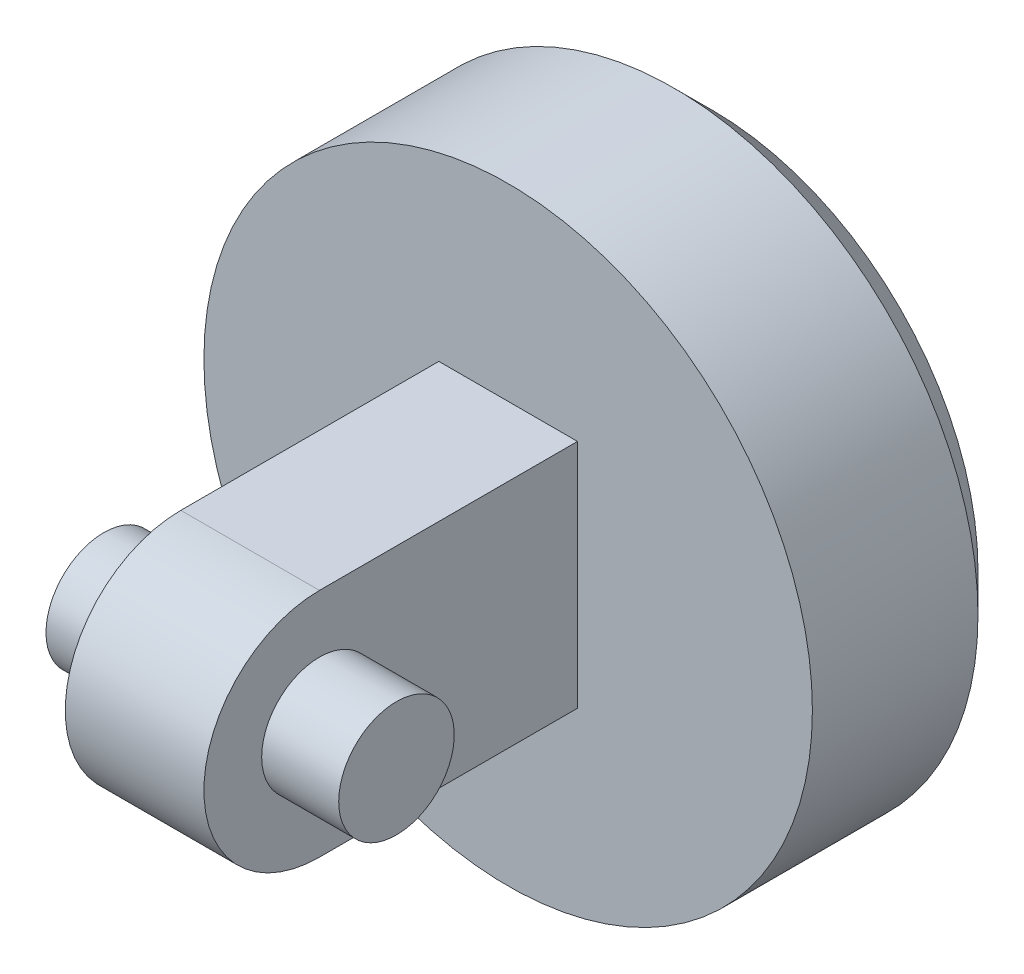
SolidWorks part; units mm, degrees
ref_plane "前视基准面" through (0, 0, 0) normal (0, 0, 1) x (1, 0, 0)
ref_plane "上视基准面" through (0, 0, 0) normal (0, 1, 0) x (1, 0, 0)
ref_plane "右视基准面" through (0, 0, 0) normal (1, 0, 0) x (0, 0, -1)
sketch "草图1" plane through (0, 0, 0) normal (0, 0, 1) x (1, 0, 0)
  circle A0 centre (0, 0) radius 7.9
  dimension "D1" = 15.8
extrude "凸台-拉伸1" add sketch "草图1" along normal blind 5.3
sketch "草图2" plane through (0, 0, 5.3) normal (0, 0, 1) x (1, 0, 0)
  line L1 (-1.8, -3) -> (1.8, -3)
  line L2 (-1.8, -3) -> (-1.8, 3)
  line L3 (-1.8, 3) -> (1.8, 3)
  line L4 (1.8, -3) -> (1.8, 3)
  line L5 (-1.8, -3) -> (1.8, 3) construction
  line L6 (-1.8, 3) -> (1.8, -3) construction
  point P0 (0, 0)
  dimension "D1" = 3.6
  dimension "D2" = 6
extrude "凸台-拉伸2" add sketch "草图2" along normal blind 9.7
sketch "草图3" plane through (-1.8, 0, 0) normal (-1, 0, 0) x (0, 0, 1)
  line L0 (15, 3) -> (15, -3) construction
  line L1 (12, -3) -> (12, 3) construction
  arc A0 (12, -3) -> (12, 3) centre (12, 0) ccw
extrude "切除-拉伸1" cut sketch "草图3" against normal through all and the other way through all flip side to cut
sketch "草图4" plane through (-1.8, 0, 0) normal (-1, 0, 0) x (0, 0, 1)
  circle A0 centre (12, 0) radius 1.5
  dimension "D1" = 3
chamfer "倒角1" distance 1 angle 45 1 edges at (7.9, 0, 0)
extrude "凸台-拉伸3" add sketch "草图4" along normal blind 2
mirror "镜向1" about plane through (0, 0, 0) normal (1, 0, 0) of "凸台-拉伸3"
